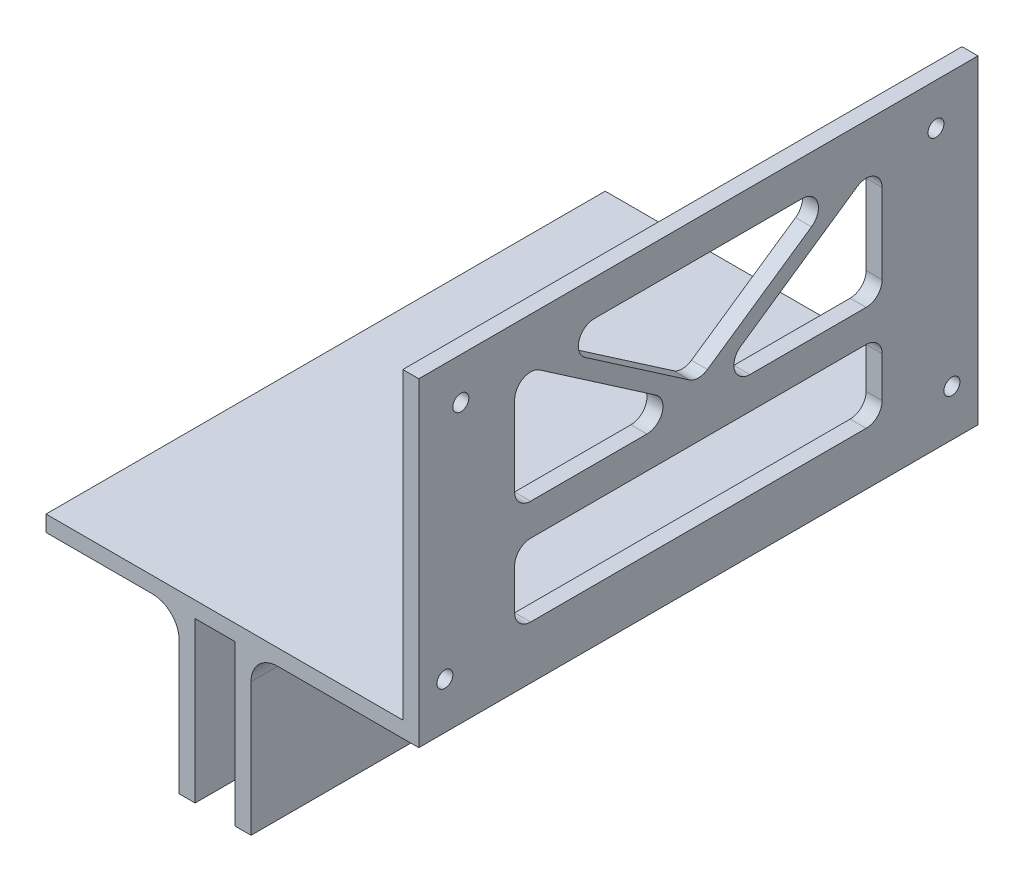
SolidWorks part; units mm, degrees
ref_plane "Front Plane" through (0, 0, 0) normal (0, 0, 1) x (1, 0, 0)
ref_plane "Top Plane" through (0, 0, 0) normal (0, 1, 0) x (1, 0, 0)
ref_plane "Right Plane" through (0, 0, 0) normal (1, 0, 0) x (0, 0, -1)
sketch "Sketch2" plane through (0, 0, 0) normal (0, 0, 1) x (1, 0, 0)
  line L0 (18.505, 30) -> (45, 30)
  line L1 (0, 0) -> (3, 0)
  line L2 (0, 0) -> (0, 25)
  line L4 (3, 0) -> (3, 30)
  line L5 (0, 33) -> (42, 33)
  line L7 (3, 30) -> (10.505, 30)
  line L10 (45, 30) -> (45, 90)
  line L11 (45, 90) -> (42, 90)
  line L12 (42, 33) -> (42, 90)
  line L14 (10.505, 30) -> (10.505, 0)
  line L15 (10.505, 0) -> (13.505, 0)
  line L16 (13.505, 25) -> (13.505, 0)
  line L18 (0, 33) -> (-25, 33)
  line L20 (-5, 30) -> (-25, 30)
  line L21 (-25, 33) -> (-25, 30)
  arc A0 (18.505, 30) -> (13.505, 25) centre (18.505, 25) ccw
  arc A1 (0, 25) -> (-5, 30) centre (-5, 25) ccw
  point P20 (0, 30)
  dimension "D10" = 5
  dimension "D1" = 7.505
  dimension "D2" = 3
  dimension "D3" = 3
  dimension "D4" = 3
  dimension "D5" = 3
  dimension "D6" = 60
  dimension "D7" = 45
  dimension "D8" = 3
  dimension "D9" = 25
  dimension "D11" = 25
  dimension "D12" = 25
extrude "Boss-Extrude1" add sketch "Sketch2" along normal blind 105
sketch "Sketch3" plane through (0, 0, 0) normal (-1, 0, 0) x (0, 0, 1)
  line L0 (52.5, 0) -> (52.5, 25) construction
  line L1 (105, 0) -> (0, 0) construction
  line L2 (105, 25) -> (0, 25) construction
  line L3 (105, 30) -> (0, 30) construction
  circle A0 centre (26.25, 20.25) radius 2.75
  circle A1 centre (78.75, 20.25) radius 2.75
  dimension "D1" = 5.5
  dimension "D2" = 26.25
  dimension "D3" = 9.75
extrude "Cut-Extrude1" cut sketch "Sketch3" against normal through all
sketch "Sketch5" plane through (42, 0, 0) normal (-1, 0, 0) x (0, 0, 1)
  line L0 (52.5, 33) -> (52.5, 90) construction
  line L1 (105, 33) -> (0, 33) construction
  line L2 (105, 90) -> (0, 90) construction
  circle A4 centre (4.9, 38.71) radius 1.5
  circle A5 centre (100.1, 38.71) radius 1.5
  circle A6 centre (7.8929, 82.1871) radius 1.5
  circle A7 centre (97.1071, 82.1871) radius 1.5
  dimension "D1" = 3
  dimension "D2" = 95.2
  dimension "D3" = 5.71
  dimension "D4" = 3
  dimension "D5" = 43.58
extrude "Cut-Extrude2" cut sketch "Sketch5" against normal through all
sketch "Sketch7" plane through (0, 0, 0) normal (0, 0, -1) x (-1, 0, 0)
  line L1 (-18.505, 30) -> (6.3663, 30)
  line L2 (-18.505, 30) -> (-18.505, 0)
  line L3 (-18.505, 0) -> (6.3663, 0)
  line L4 (6.3663, 30) -> (6.3663, 0)
extrude "Cut-Extrude5" cut sketch "Sketch7" against normal blind 19.5 contours L2 L3 L4 L1
fillet "Fillet1" radius 19.5 2 edges at (-1, 30, 19.5) (14.505, 30, 19.5)
sketch "Sketch9" plane through (42, 0, 0) normal (-1, 0, 0) x (0, 0, 1)
  line L0 (105, 90) -> (105, 33) construction
  line L1 (21, 53.5679) -> (84, 53.5679)
  line L2 (18, 50.5679) -> (18, 42.9387)
  line L3 (21, 39.9387) -> (84, 39.9387)
  line L4 (87, 50.5679) -> (87, 42.9387)
  line L5 (0, 90) -> (0, 33) construction
  line L9 (22.6989, 80.0739) -> (44.5352, 65.0702)
  line L10 (21, 59.5976) -> (42.8363, 59.5976)
  line L11 (105, 33) -> (0, 33) construction
  line L27 (52.5, 53.5679) -> (52.5, 33) construction
  line L31 (18, 62.5976) -> (18, 77.6013)
  line L32 (32.9612, 83.3025) -> (72.0388, 83.3025)
  line L34 (31.2623, 77.8299) -> (50.8011, 64.4049)
  line L35 (19.6989, 85.7751) -> (54.1989, 62.0702) construction
  line L36 (82.3011, 80.0739) -> (60.4648, 65.0702)
  line L37 (87, 62.5976) -> (87, 77.6013)
  line L38 (73.7377, 77.8299) -> (54.1989, 64.4049)
  line L39 (18, 83.3025) -> (52.5, 59.5976) construction
  line L40 (62.1637, 59.5976) -> (84, 59.5976)
  arc A3 (84, 39.9387) -> (87, 42.9387) centre (84, 42.9387) ccw
  arc A4 (84, 53.5679) -> (87, 50.5679) centre (84, 50.5679) cw
  arc A5 (21, 53.5679) -> (18, 50.5679) centre (21, 50.5679) ccw
  arc A6 (18, 42.9387) -> (21, 39.9387) centre (21, 42.9387) ccw
  arc A8 (72.0388, 83.3025) -> (73.7377, 77.8299) centre (72.0388, 80.3025) cw
  arc A9 (32.9612, 83.3025) -> (31.2623, 77.8299) centre (32.9612, 80.3025) ccw
  arc A10 (54.1989, 64.4049) -> (50.8011, 64.4049) centre (52.5, 66.8774) cw
  arc A11 (82.3011, 80.0739) -> (87, 77.6013) centre (84, 77.6013) cw
  arc A12 (42.8363, 59.5976) -> (44.5352, 65.0702) centre (42.8363, 62.5976) ccw
  arc A13 (21, 59.5976) -> (18, 62.5976) centre (21, 62.5976) cw
  arc A14 (18, 77.6013) -> (22.6989, 80.0739) centre (21, 77.6013) cw
  arc A15 (87, 62.5976) -> (84, 59.5976) centre (84, 62.5976) cw
  arc A16 (60.4648, 65.0702) -> (62.1637, 59.5976) centre (62.1637, 62.5976) ccw
  point P24 (81.7025, 83.3025)
  point P33 (18, 39.9387)
  point P36 (23.2975, 83.3025)
  point P39 (52.5, 63.2375)
  point P42 (87, 83.3025)
  point P46 (85.2152, 34.9387)
  point P49 (52.5, 45.3004)
  dimension "D3" = 3
  dimension "D4" = 3
  dimension "D6" = 3
  dimension "D7" = 3
  dimension "D1" = 18
  dimension "D2" = 18
  dimension "D5" = 5
extrude "Cut-Extrude6" cut sketch "Sketch9" against normal through all
